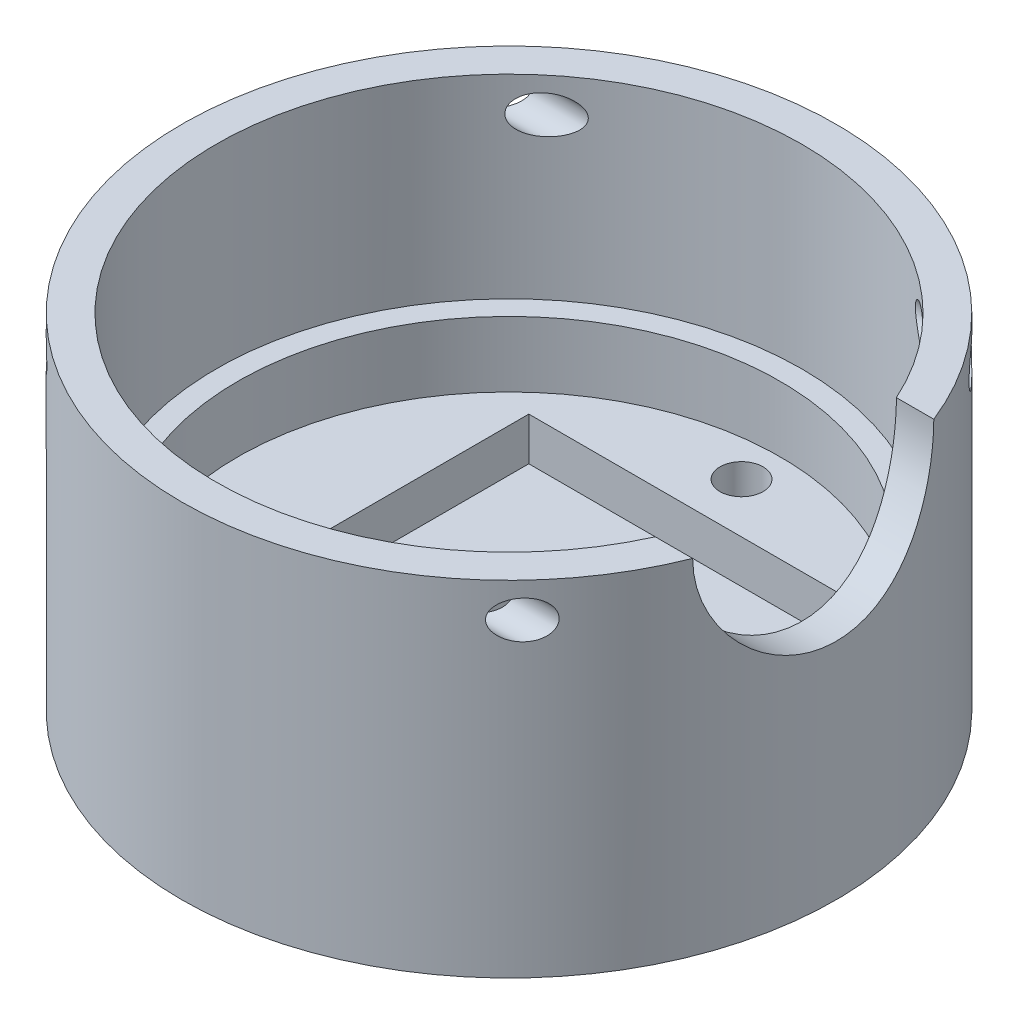
SolidWorks part; units mm, degrees
ref_plane "Front Plane" through (0, 0, 0) normal (0, 0, 1) x (1, 0, 0)
ref_plane "Top Plane" through (0, 0, 0) normal (0, 1, 0) x (1, 0, 0)
ref_plane "Right Plane" through (0, 0, 0) normal (1, 0, 0) x (0, 0, -1)
sketch "Sketch3" plane through (0, 0, 0) normal (0, 1, 0) x (1, 0, 0)
  circle A0 centre (0, 0) radius 19
  dimension "D1" = 38
extrude "Main Body" add sketch "Sketch3" against normal blind 20
sketch "Sketch5" plane through (0, -20, 0) normal (0, -1, 0) x (1, 0, 0)
  circle A0 centre (0, 0) radius 17
  circle A1 centre (0, 0) radius 19 construction
  dimension "D1" = 2
extrude "Cut for Headers" cut sketch "Sketch5" against normal through all from offset 8.7 offset against normal yes
ref_axis "Central Axis" through (0, 1, 0) along (0, -1, 0)
ref_axis "Horizontal Axis" through (-20.9, 0, 0) along (1, 0, 0)
ref_axis "Vertical Axis" through (0, 0, -20.9) along (0, 0, 1)
sketch "Sketch7" plane through (0, 0, 0) normal (1, 0, 0) x (0, 0, -1)
  circle A0 centre (0, 0) radius 7
  point P3 (0, -3.3432)
  dimension "D1" = 14
extrude "Cut for ADNS Wires" cut sketch "Sketch7" along normal up to next
sketch "Sketch8" plane through (0, -11.3, 0) normal (0, 1, 0) x (1, 0, 0)
  circle A0 centre (0, 0) radius 15.75
  dimension "D1" = 31.5
extrude "Cut for PCB" cut sketch "Sketch8" against normal blind 3.8
sketch "Sketch9" plane through (0, -15.1, 0) normal (0, 1, 0) x (1, 0, 0)
  line L0 (0, 15.75) -> (0, -15.75) construction
  line L1 (-15.75, 0) -> (15.75, 0) construction
  circle A1 centre (0, 0) radius 15.75 construction
  circle A2 centre (0, 13.5) radius 1.25
  circle A3 centre (0, -13.5) radius 1.25
  point P0 (0, 0)
  dimension "D1" = 2.5
  dimension "D2" = 27
extrude "Cut for Screw Holes" cut sketch "Sketch9" against normal blind 5
sketch "Sketch10" plane through (0, -15.1, 0) normal (0, 1, 0) x (1, 0, 0)
  line L1 (-9.45, -10.6) -> (9.45, -10.6)
  line L2 (-9.45, -10.6) -> (-9.45, 10.6)
  line L3 (-9.45, 10.6) -> (9.45, 10.6)
  line L4 (9.45, -10.6) -> (9.45, 10.6)
  line L5 (-9.45, -10.6) -> (9.45, 10.6) construction
  line L6 (-9.45, 10.6) -> (9.45, -10.6) construction
  point P0 (0, 0)
  dimension "D1" = 18.9
  dimension "D2" = 21.2
extrude "Cut for Lens" cut sketch "Sketch10" against normal blind 2.5
sketch "Sketch11" plane through (0, -17.6, 0) normal (0, 1, 0) x (1, 0, 0)
  line L1 (-4.1, -5.1) -> (4.1, -5.1)
  line L2 (-4.1, -5.1) -> (-4.1, 5.1)
  line L3 (-4.1, 5.1) -> (4.1, 5.1)
  line L4 (4.1, -5.1) -> (4.1, 5.1)
  line L5 (-4.1, -5.1) -> (4.1, 5.1) construction
  line L6 (-4.1, 5.1) -> (4.1, -5.1) construction
  point P0 (0, 0)
  dimension "D1" = 10.2
  dimension "D2" = 8.2
extrude "Cut for Pupil" cut sketch "Sketch11" against normal up to next
sketch "Sketch13" plane through (0, 0, 0) normal (1, 0, 0) x (0, 0, -1)
  line L0 (0, 1) -> (0, -21) construction
  line L1 (20.9, 0) -> (-20.9, 0) construction
  circle A0 centre (13, -2) radius 1.1
  circle A1 centre (-13, -2) radius 1.1
  point P0 (13, -2)
  point P7 (-13, -2)
  dimension "D3" = 2.2
  dimension "D4" = 13
  dimension "D5" = 2.2
  dimension "D1" = 13
  dimension "D2" = 2
extrude "Cuts for Body Screw Holes" cut sketch "Sketch13" against normal through all both and the other way through all
